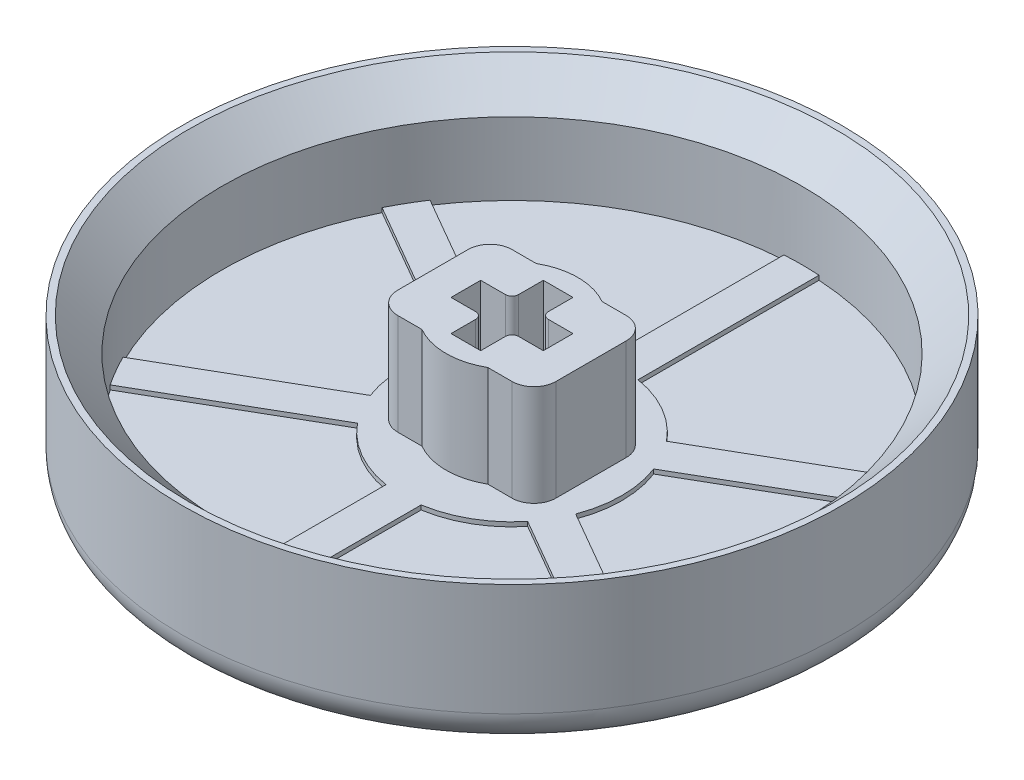
SolidWorks part; units mm, degrees
ref_plane "Front Plane" through (0, 0, 0) normal (0, 0, 1) x (1, 0, 0)
ref_plane "Top Plane" through (0, 0, 0) normal (0, 1, 0) x (1, 0, 0)
ref_plane "Right Plane" through (0, 0, 0) normal (1, 0, 0) x (0, 0, -1)
sketch "Sketch1" plane through (0, 0, 0) normal (0, 1, 0) x (1, 0, 0)
  circle A0 centre (0, 0) radius 15
  dimension "D1" = 30
extrude "button top" add sketch "Sketch1" along normal blind 1.8
sketch "Sketch2" plane through (0, 1.8, 0) normal (0, 1, 0) x (1, 0, 0)
  circle A3 centre (0, 0) radius 15
  circle A4 centre (0, 0) radius 15 construction
  circle A5 centre (0, 0) radius 13.2
  dimension "D1" = 1.8
extrude "button walls" add sketch "Sketch2" along normal blind 4.8
sketch "Sketch5" plane through (0, 1.8, 0) normal (0, 1, 0) x (1, 0, 0)
  circle A0 centre (0, 0) radius 5
  dimension "D1" = 10
extrude "offset" add sketch "Sketch5" along normal blind 0.2
sketch "Sketch3" plane through (0, 1.8, 0) normal (0, 1, 0) x (1, 0, 0)
  line L0 (0, -2.1) -> (0, 2.1) construction
  line L1 (-2.1, 0) -> (2.1, 0) construction
  line L2 (-0.675, 0.975) -> (-0.675, 2.1)
  line L3 (-0.675, -2.1) -> (0.675, -2.1)
  line L4 (-0.675, -2.1) -> (-0.675, -0.975)
  line L5 (-0.675, 2.1) -> (0.675, 2.1)
  line L6 (0.675, -2.1) -> (0.675, -0.975)
  line L7 (-0.675, -2.1) -> (0.675, 2.1) construction
  line L8 (-0.675, 2.1) -> (0.675, -2.1) construction
  line L9 (-2.1, -0.675) -> (-0.975, -0.675)
  line L10 (-2.1, -0.675) -> (-2.1, 0.675)
  line L11 (-2.1, 0.675) -> (-0.975, 0.675)
  line L12 (2.1, -0.675) -> (2.1, 0.675)
  line L13 (-2.1, -0.675) -> (2.1, 0.675) construction
  line L14 (-2.1, 0.675) -> (2.1, -0.675) construction
  line L15 (0.975, 0.675) -> (2.1, 0.675)
  line L16 (0.675, 0.975) -> (0.675, 2.1)
  line L17 (0.975, -0.675) -> (2.1, -0.675)
  line L19 (-3.6, -2.6) -> (3.6, -2.6)
  line L20 (-3.6, -2.6) -> (-3.6, 2.6)
  line L21 (-3.6, 2.6) -> (3.6, 2.6)
  line L22 (3.6, -2.6) -> (3.6, 2.6)
  line L23 (-3.6, -2.6) -> (3.6, 2.6) construction
  line L24 (-3.6, 2.6) -> (3.6, -2.6) construction
  arc A1 (-0.675, -0.975) -> (-0.975, -0.675) centre (-0.975, -0.975) ccw
  arc A2 (0.675, -0.975) -> (0.975, -0.675) centre (0.975, -0.975) cw
  arc A3 (0.975, 0.675) -> (0.675, 0.975) centre (0.975, 0.975) cw
  arc A4 (-0.675, 0.975) -> (-0.975, 0.675) centre (-0.975, 0.975) cw
  circle A5 centre (0, 0) radius 3
  point P0 (0, 0)
  point P6 (0, 0)
  point P9 (0, 0)
  point P22 (2.1, 0)
  point P24 (0, 2.1)
  point P29 (0.675, -0.675)
  point P32 (0.675, 0.675)
  dimension "D1" = 7.2
  dimension "D4" = 0.3
  dimension "D6" = 6
  dimension "D2" = 4.2
  dimension "D3" = 1.35
  dimension "D5" = 5.2
extrude "stem housing" add sketch "Sketch3" along normal blind 4.6 from surface contours A5 L21 L20 L19 | L19 A5 L21 A4 L2 L5 L16 A3 L15 L12 L17 A2 L6 L3 L4 A1 L9 L10 L11 | A5 L19 L22 L21 | L21 A5 | L19 A5 region at (-3.5439, 1.8, 0) region at (-2.9206, 1.8, 0) region at (0, 1.8, 2.761) region at (2.6457, 1.8, 1.5297) region at (0, 1.8, -2.761) starting at face at (0, 2, 5)
sketch "Sketch4" plane through (0, 1.8, 0) normal (0, 1, 0) x (1, 0, 0)
  line L0 (0, 3.3382) -> (0, 13.2) construction
  line L1 (-0.8, 3.3382) -> (-0.8, 13.2)
  line L2 (0.8, 3.3382) -> (0.8, 13.2)
  line L3 (2.8909, 1.6691) -> (11.4315, 6.6) construction
  line L4 (2.4909, 2.3619) -> (11.0315, 7.2928)
  line L5 (3.2909, 0.9763) -> (11.8315, 5.9072)
  line L6 (2.8909, -1.6691) -> (11.4315, -6.6) construction
  line L7 (3.2909, -0.9763) -> (11.8315, -5.9072)
  line L8 (2.4909, -2.3619) -> (11.0315, -7.2928)
  line L9 (0, -3.3382) -> (0, -13.2) construction
  line L10 (0.8, -3.3382) -> (0.8, -13.2)
  line L11 (-0.8, -3.3382) -> (-0.8, -13.2)
  line L12 (-2.8909, -1.6691) -> (-11.4315, -6.6) construction
  line L13 (-2.4909, -2.3619) -> (-11.0315, -7.2928)
  line L14 (-3.2909, -0.9763) -> (-11.8315, -5.9072)
  line L15 (-2.8909, 1.6691) -> (-11.4315, 6.6) construction
  line L16 (-3.2909, 0.9763) -> (-11.8315, 5.9072)
  line L17 (-2.4909, 2.3619) -> (-11.0315, 7.2928)
  circle A2 centre (0, 0) radius 13.2 construction
  arc A3 (-0.8, 3.3382) -> (0.8, 3.3382) centre (0, 3.3382) ccw
  arc A4 (0.8, 13.2) -> (-0.8, 13.2) centre (0, 13.2) ccw
  arc A5 (2.4909, 2.3619) -> (3.2909, 0.9763) centre (2.8909, 1.6691) ccw
  arc A6 (11.8315, 5.9072) -> (11.0315, 7.2928) centre (11.4315, 6.6) ccw
  arc A7 (3.2909, -0.9763) -> (2.4909, -2.3619) centre (2.8909, -1.6691) ccw
  arc A8 (11.0315, -7.2928) -> (11.8315, -5.9072) centre (11.4315, -6.6) ccw
  arc A9 (0.8, -3.3382) -> (-0.8, -3.3382) centre (0, -3.3382) ccw
  arc A10 (-0.8, -13.2) -> (0.8, -13.2) centre (0, -13.2) ccw
  arc A11 (-2.4909, -2.3619) -> (-3.2909, -0.9763) centre (-2.8909, -1.6691) ccw
  arc A12 (-11.8315, -5.9072) -> (-11.0315, -7.2928) centre (-11.4315, -6.6) ccw
  arc A13 (-3.2909, 0.9763) -> (-2.4909, 2.3619) centre (-2.8909, 1.6691) ccw
  arc A14 (-11.0315, 7.2928) -> (-11.8315, 5.9072) centre (-11.4315, 6.6) ccw
  point P9 (0, 8.2691)
  point P18 (7.1612, 4.1345)
  point P25 (7.1612, -4.1345)
  point P32 (0, -8.2691)
  point P39 (-7.1612, -4.1345)
  point P46 (-7.1612, 4.1345)
  point P51 (0, 0)
  dimension "D1" = 1.6
  dimension "D2" = 6
extrude "spokes" add sketch "Sketch4" along normal up to surface (0.2 mm away) up to face at (0, 2, 5)
fillet "Fillet1" radius 1.5 1 edges at (0, 0, 15)
chamfer "Chamfer1" distance 1.5 angle 45 1 edges at (0, 6.6, 13.2)
fillet "Fillet2" radius 1 4 edges at (-3.6, 4.3, -2.6) (-3.6, 4.3, 2.6) (3.6, 4.3, -2.6) (3.6, 4.3, 2.6)
